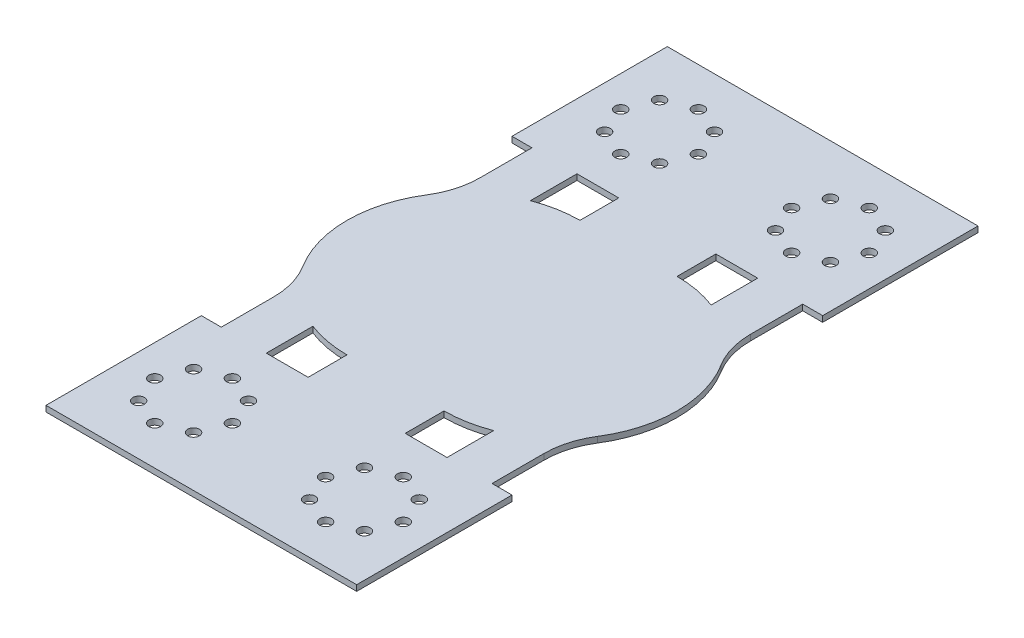
SolidWorks part; units mm, degrees
ref_plane "Alzado" through (0, 0, 0) normal (0, 0, 1) x (1, 0, 0)
ref_plane "Planta" through (0, 0, 0) normal (0, 1, 0) x (1, 0, 0)
ref_plane "Vista lateral" through (0, 0, 0) normal (1, 0, 0) x (0, 0, -1)
sketch "Croquis1" plane through (0, 0, 0) normal (0, 1, 0) x (1, 0, 0)
  line L0 (-40, -40) -> (40, -40)
  line L1 (40, -40) -> (40, 0)
  line L2 (40, 0) -> (12.5, 0)
  line L3 (12.5, 0) -> (12.5, 80)
  line L4 (12.5, 80) -> (40, 80)
  line L5 (40, 80) -> (40, 120)
  line L6 (40, 120) -> (-40, 120)
  line L7 (-40, 120) -> (-40, 80)
  line L8 (-40, 80) -> (-12.5, 80)
  line L9 (-12.5, 80) -> (-12.5, 0)
  line L10 (-12.5, 0) -> (-40, 0)
  line L11 (-40, 0) -> (-40, -40)
  line L12 (12.5, 0) -> (-12.5, 0) construction
  line L13 (0, -40) -> (0, 120) construction
  line L15 (-12.5, 0) -> (-12.5, 40)
  line L16 (-34.8607, 80) -> (-34.8607, 60)
  line L18 (-23.2703, 80) -> (-23.2703, 68)
  line L19 (34.8607, 80) -> (34.8607, 60)
  line L20 (23.2703, 80) -> (23.2703, 68)
  line L21 (-12.5, 40) -> (12.5, 40) construction
  line L22 (34.8607, 0) -> (34.8607, 20)
  line L23 (23.2703, 0) -> (23.2703, 12)
  line L24 (-23.2703, 0) -> (-23.2703, 12)
  line L25 (-34.8607, 0) -> (-34.8607, 20)
  arc A2 (12.5, 70) -> (12.5, 10) centre (12.5, 40) cw
  arc A3 (-12.5, 70) -> (-12.5, 10) centre (-12.5, 40) ccw
  point P12 (0, -40)
  point P13 (0, 120)
  point P15 (0, 0)
  point P23 (-12.5, 40)
  dimension "D6" = 20
  dimension "D5" = 30
  dimension "D1" = 40
  dimension "D2" = 80
  dimension "D3" = 80
  dimension "D4" = 25
  dimension "D7" = 12
  dimension "D8" = 160
extrude "Saliente-Extruir1" add sketch "Croquis1" along normal blind 1.5 contours A2 L3 | L10 L11 L0 L1 L2 L3 L4 L5 L6 L7 L8 L9 L15 | L9 A3 | L22 A2 L23 L2 | L20 A2 L19 L4 | A3 L18 L8 L16 | A3 L25 L10 L24 region at (0, 0, -40) region at (-29.5614, 0, -7.8308) region at (29.5614, 0, -7.8308) region at (-25.2324, 0, -40) region at (25.2324, 0, -40) region at (-29.5614, 0, -72.1692) region at (29.5614, 0, -72.1692)
sketch "Croquis2" plane through (0, 1.5, 0) normal (0, 1, 0) x (1, 0, 0)
  line L0 (40, -20) -> (-40, -20) construction
  line L1 (40, -40) -> (40, 0) construction
  line L2 (-40, 0) -> (-40, -40) construction
  line L3 (0, 120) -> (0, -40) construction
  line L4 (40, 120) -> (-40, 120) construction
  line L5 (-40, -40) -> (40, -40) construction
  line L6 (-42.5, 40) -> (42.5, 40) construction
  circle A0 centre (32, -20) radius 1.5
  circle A1 centre (29.0711, -27.0711) radius 1.5
  circle A2 centre (22, -30) radius 1.5
  circle A3 centre (14.9289, -27.0711) radius 1.5
  circle A4 centre (12, -20) radius 1.5
  circle A5 centre (14.9289, -12.9289) radius 1.5
  circle A6 centre (22, -10) radius 1.5
  circle A7 centre (29.0711, -12.9289) radius 1.5
  arc A8 (-34.8607, 60) -> (-34.8607, 20) centre (-12.5, 40) ccw construction
  arc A9 (34.8607, 20) -> (34.8607, 60) centre (12.5, 40) ccw construction
  circle A10 centre (-29.0711, -12.9289) radius 1.5
  circle A11 centre (-22, -10) radius 1.5
  circle A12 centre (-14.9289, -12.9289) radius 1.5
  circle A13 centre (-12, -20) radius 1.5
  circle A14 centre (-14.9289, -27.0711) radius 1.5
  circle A15 centre (-22, -30) radius 1.5
  circle A16 centre (-29.0711, -27.0711) radius 1.5
  circle A17 centre (-32, -20) radius 1.5
  circle A18 centre (-32, 100) radius 1.5
  circle A19 centre (-29.0711, 107.0711) radius 1.5
  circle A20 centre (-22, 110) radius 1.5
  circle A21 centre (-14.9289, 107.0711) radius 1.5
  circle A22 centre (-12, 100) radius 1.5
  circle A23 centre (-14.9289, 92.9289) radius 1.5
  circle A24 centre (-22, 90) radius 1.5
  circle A25 centre (-29.0711, 92.9289) radius 1.5
  circle A26 centre (29.0711, 92.9289) radius 1.5
  circle A27 centre (22, 90) radius 1.5
  circle A28 centre (14.9289, 92.9289) radius 1.5
  circle A29 centre (12, 100) radius 1.5
  circle A30 centre (14.9289, 107.0711) radius 1.5
  circle A31 centre (22, 110) radius 1.5
  circle A32 centre (29.0711, 107.0711) radius 1.5
  circle A33 centre (32, 100) radius 1.5
  point P8 (22, -20)
  point P25 (22, -20)
  point P54 (-22, -20)
  point P87 (-22, 100)
  point P88 (22, 100)
  dimension "D1" = 3
  dimension "D2" = 8
  dimension "D3" = 10
  dimension "D4" = 8
extrude "Cortar-Extruir1" cut sketch "Croquis2" against normal blind 1.5
fillet "Redondeo1" radius 20 4 edges at (-34.8607, 0.75, -60) (-34.8607, 0.75, -20) (34.8607, 0.75, -20) (34.8607, 0.75, -60)
